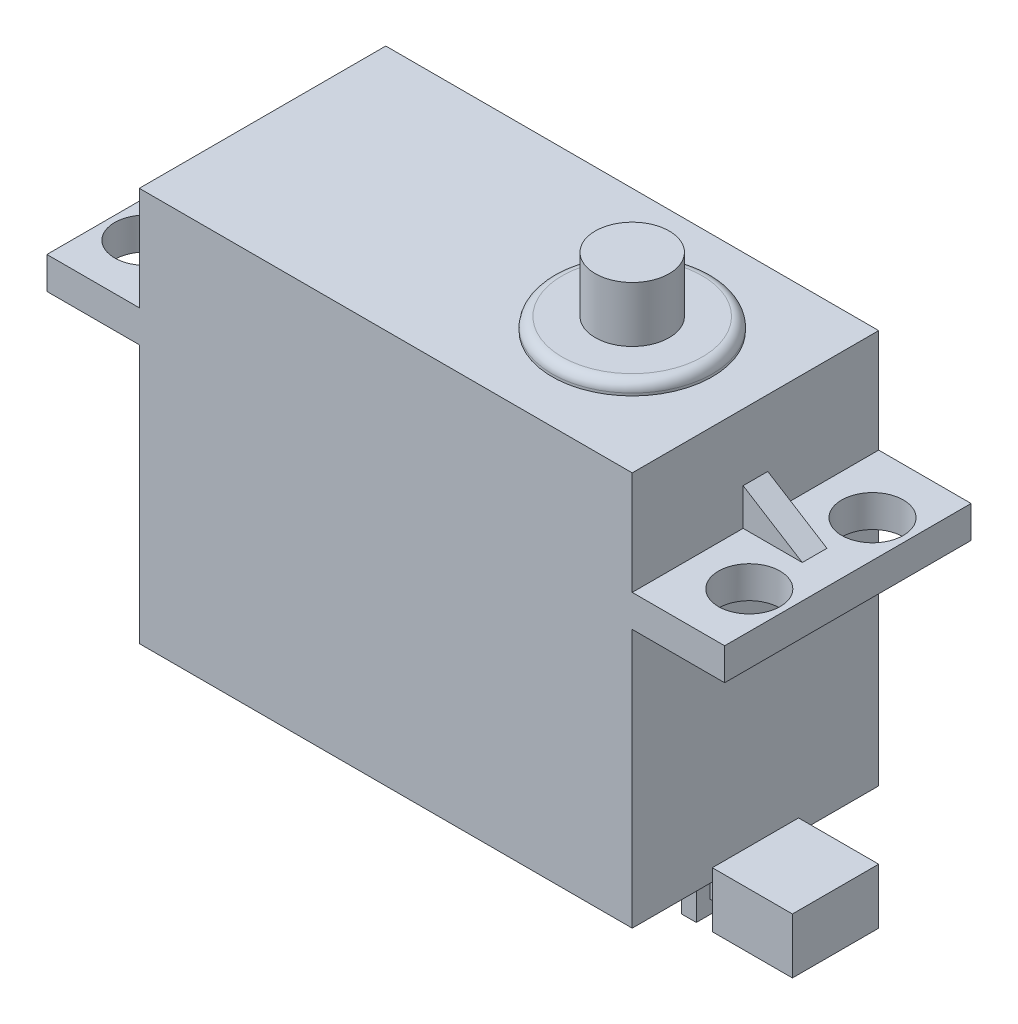
SolidWorks part; units mm, degrees
ref_plane "Face" through (0, 0, 0) normal (0, 0, 1) x (1, 0, 0)
ref_plane "Dessus" through (0, 0, 0) normal (0, 1, 0) x (1, 0, 0)
ref_plane "Droite" through (0, 0, 0) normal (1, 0, 0) x (0, 0, -1)
sketch "Esquisse1" plane through (0, 0, 0) normal (0, 0, 1) x (1, 0, 0)
  line L1 (0, 32) -> (40, 32)
  line L2 (0, 32) -> (0, 0)
  line L3 (0, 0) -> (40, 0)
  line L4 (40, 32) -> (40, 0)
  dimension "D1" = 40
  dimension "D2" = 32
extrude "Extrusion1" add sketch "Esquisse1" along normal mid plane 20
sketch "Esquisse2" plane through (0, 32, 0) normal (0, 1, 0) x (-1, 0, 0)
  line L0 (-41.477, 0) -> (-8.6336, 0) construction
  line L1 (-40, 10) -> (0, 10) construction
  line L2 (-40, -10) -> (0, -10) construction
  line L3 (-40, 10) -> (-40, -10) construction
  circle A0 centre (-30, 0) radius 6.5
  dimension "D2" = 13
  dimension "D1" = 10
extrude "Extrusion2" add sketch "Esquisse2" along normal blind 1
fillet "Congé1" radius 0.8 1 edges at (30, 33, 6.5)
sketch "Esquisse3" plane through (0, 33, 0) normal (0, 1, 0) x (-1, 0, 0)
  circle A0 centre (-30, 0) radius 3
  circle A1 centre (-30, 0) radius 5.7 construction
  dimension "D1" = 6
extrude "Extrusion3" add sketch "Esquisse3" along normal blind 4.5
sketch "Esquisse4" plane through (0, 0, 0) normal (0, -1, 0) x (1, 0, 0)
  line L0 (43.8501, 0) -> (17.0846, 0) construction
  line L1 (46.5, 3.5) -> (37.5, 3.5)
  line L2 (46.5, 3.5) -> (46.5, -3.5)
  line L3 (46.5, -3.5) -> (37.5, -3.5)
  line L4 (37.5, 3.5) -> (37.5, -3.5)
  line L5 (0, -10) -> (40, -10) construction
  line L6 (0, 10) -> (40, 10) construction
  line L7 (40, 10) -> (40, -10) construction
  dimension "D1" = 7
  dimension "D2" = 9
  dimension "D3" = 2.5
extrude "Extrusion4" add sketch "Esquisse4" along normal blind 3.5 and the other way blind 1
sketch "Esquisse5" plane through (0, -3.5, 0) normal (0, -1, 0) x (1, 0, 0)
  line L0 (48.3745, 0) -> (28.0451, 0) construction
  line L1 (37.5, -3.5) -> (46.5, -3.5) construction
  line L2 (46.5, 3.5) -> (37.5, 3.5) construction
  line L4 (40, 3.5) -> (38.7, 3.5)
  line L5 (40, 3.5) -> (40, 2.4)
  line L6 (40, 2.4) -> (38.7, 2.4)
  line L7 (38.7, 3.5) -> (38.7, 2.4)
  line L8 (38.7, -3.5) -> (38.7, -2.4)
  line L9 (40, -2.4) -> (38.7, -2.4)
  line L10 (40, -3.5) -> (40, -2.4)
  line L11 (40, -3.5) -> (38.7, -3.5)
  line L13 (40, -3.5) -> (40, -10) construction
  dimension "D1" = 1.1
  dimension "D2" = 1.3
extrude "Enlèv. mat.-Extru.2" cut sketch "Esquisse5" against normal up to surface (3.5 mm away) up to face at (29.375, 0, 0)
sketch "Esquisse9" plane through (0, 0, -2.4) normal (0, 0, -1) x (-1, 0, 0)
  line L0 (-40, 0) -> (-40, -3.5) construction
  line L1 (-40, -2.4) -> (-38.7, -2.4)
  line L2 (-40, -2.4) -> (-40, -3.5)
  line L3 (-40, -3.5) -> (-38.7, -3.5)
  line L4 (-38.7, -2.4) -> (-38.7, -3.5)
  dimension "D1" = 1.1
extrude "Enlèv. mat.-Extru.5" cut sketch "Esquisse9" against normal up to next
sketch "Esquisse7" plane through (0, 0, 0) normal (0, -1, 0) x (1, 0, 0)
  line L0 (47.8232, 0) -> (-2.4258, 0) construction
  line L1 (20, 31.6197) -> (20, -15.8759) construction
  line L2 (0, -10) -> (40, -10) construction
  line L3 (0, 10) -> (40, 10) construction
  line L4 (0, 10) -> (0, -10) construction
  line L5 (40, -3.5) -> (40, -10) construction
  circle A0 centre (37.3, -7.3) radius 1
  circle A1 centre (2.7, -7.3) radius 1
  circle A2 centre (2.7, 7.3) radius 1
  circle A3 centre (37.3, 7.3) radius 1
  dimension "D1" = 2
  dimension "D2" = 2.7
  dimension "D3" = 2.7
extrude "Enlèv. mat.-Extru.4" cut sketch "Esquisse7" against normal blind 4.5
sketch "Esquisse8" plane through (0, 0, 10) normal (0, 0, 1) x (1, 0, 0)
  line L0 (20, 34.4268) -> (20, 1.6955) construction
  line L1 (40, 0) -> (40, 32) construction
  line L2 (0, 32) -> (0, 0) construction
  line L3 (0, 0) -> (40, 0) construction
  line L4 (40, 23.6) -> (47.5, 23.6)
  line L5 (40, 23.6) -> (40, 21)
  line L6 (40, 21) -> (47.5, 21)
  line L7 (47.5, 23.6) -> (47.5, 21)
  line L8 (-7.5, 23.6) -> (-7.5, 21)
  line L9 (0, 21) -> (-7.5, 21)
  line L10 (0, 23.6) -> (0, 21)
  line L11 (0, 23.6) -> (-7.5, 23.6)
  dimension "D1" = 21
  dimension "D2" = 2.6
  dimension "D3" = 55
extrude "Extrusion6" add sketch "Esquisse8" against normal up to surface (20 mm away) up to face at (20, 16, -10)
sketch "Esquisse10" plane through (0, 0, 0) normal (0, 0, 1) x (1, 0, 0)
  line L0 (40, 26.6) -> (40, 23.6)
  line L1 (40, 26.6) -> (44.8, 23.6)
  line L2 (44.8, 23.6) -> (40, 23.6)
  line L3 (40, 23.6) -> (40, 32) construction
  line L4 (47.5, 23.6) -> (40, 23.6) construction
  line L5 (20, 38.6176) -> (20, 11.2323) construction
  line L6 (40, 0) -> (40, 21) construction
  line L7 (0, 21) -> (0, 0) construction
  line L8 (-4.8, 23.6) -> (0, 23.6)
  line L9 (0, 26.6) -> (-4.8, 23.6)
  line L10 (0, 26.6) -> (0, 23.6)
  dimension "D1" = 4.8
  dimension "D2" = 3
extrude "Extrusion7" add sketch "Esquisse10" along normal mid plane 2
sketch "Esquisse11" plane through (0, 23.6, 0) normal (0, 1, 0) x (-1, 0, 0)
  line L0 (-48.9719, 0) -> (10.183, 0) construction
  line L1 (-20, -23.1496) -> (-20, 28.0311) construction
  line L2 (-47.5, -10) -> (-47.5, 10) construction
  line L3 (7.5, -10) -> (7.5, 10) construction
  line L4 (-40, 10) -> (0, 10) construction
  line L5 (-40, -10) -> (0, -10) construction
  circle A0 centre (-44.5, 5) radius 2.5
  circle A1 centre (-44.5, -5) radius 2.5
  circle A2 centre (4.5, -5) radius 2.5
  circle A3 centre (4.5, 5) radius 2.5
  dimension "D1" = 5
  dimension "D2" = 10
  dimension "D3" = 3
extrude "Enlèv. mat.-Extru.6" cut sketch "Esquisse11" against normal up to next
